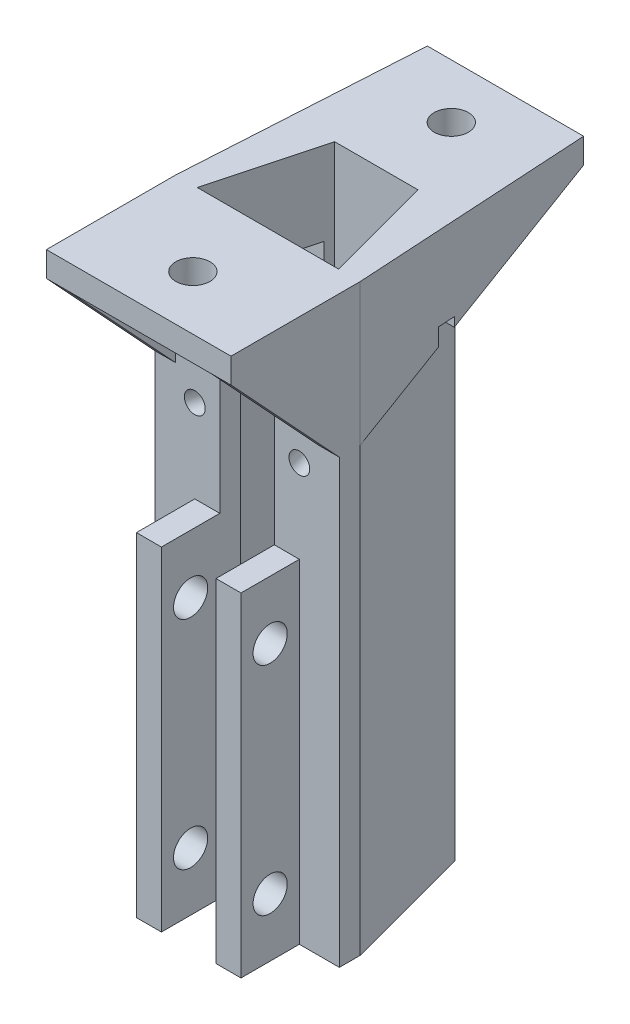
SolidWorks part; units mm, degrees
ref_plane "Front Plane" through (0, 0, 0) normal (0, 0, 1) x (1, 0, 0)
ref_plane "Top Plane" through (0, 0, 0) normal (0, 1, 0) x (1, 0, 0)
ref_plane "Right Plane" through (0, 0, 0) normal (1, 0, 0) x (0, 0, -1)
sketch "Sketch2" plane through (0, 0, 0) normal (0, 1, 0) x (1, 0, 0)
  line L0 (-8.0683, 3.8436) -> (5.7683, 3.8436)
  line L1 (-8.0683, 3.8436) -> (-8.0683, 1.3436)
  line L2 (5.7683, 3.8436) -> (5.7683, 1.3436)
  line L3 (-8.0683, 1.3436) -> (5.7683, 1.3436)
  line L4 (5.7683, 3.8436) -> (9.9215, -11.6564)
  line L5 (5.7683, 3.8436) -> (3.3535, 3.1965)
  line L6 (9.9215, -11.6564) -> (7.5067, -12.3035)
  line L7 (3.3535, 3.1965) -> (7.5067, -12.3035)
  line L8 (-8.0683, 3.8436) -> (-12.2215, -11.6564)
  line L9 (-8.0683, 3.8436) -> (-5.6535, 3.1965)
  line L10 (-12.2215, -11.6564) -> (-9.8067, -12.3035)
  line L11 (-5.6535, 3.1965) -> (-9.8067, -12.3035)
  line L12 (-12.2215, -11.6564) -> (-4.4215, -11.6564)
  line L13 (-12.2215, -11.6564) -> (-12.2215, -14.1564)
  line L14 (-4.4215, -11.6564) -> (-4.4215, -14.1564)
  line L15 (-12.2215, -14.1564) -> (-4.4215, -14.1564)
  line L16 (9.9215, -11.6564) -> (2.1215, -11.6564)
  line L17 (9.9215, -11.6564) -> (9.9215, -14.1564)
  line L18 (2.1215, -11.6564) -> (2.1215, -14.1564)
  line L19 (9.9215, -14.1564) -> (2.1215, -14.1564)
  line L20 (-4.4215, -14.1564) -> (-7.4215, -14.1564)
  line L21 (-4.4215, -14.1564) -> (-4.4215, -21.1564)
  line L22 (-7.4215, -14.1564) -> (-7.4215, -21.1564)
  line L23 (-4.4215, -21.1564) -> (-7.4215, -21.1564)
  line L24 (2.1215, -14.1564) -> (5.1215, -14.1564)
  line L25 (2.1215, -14.1564) -> (2.1215, -21.1564)
  line L26 (5.1215, -14.1564) -> (5.1215, -21.1564)
  line L27 (2.1215, -21.1564) -> (5.1215, -21.1564)
  point P0 (-6.15, 1.3436)
  point P21 (3.85, 1.3436)
  point P24 (7.3334, -11.6564)
  point P25 (-9.6333, -11.6564)
  dimension "D1" = 0
  dimension "D2" = 2.5
  dimension "D3" = 2.5
  dimension "D4" = 2.5
  dimension "D5" = 10
  dimension "D6" = 360
  dimension "D7" = 13
  dimension "D8" = 2.5
  dimension "D9" = 2.5
  dimension "D10" = 13
  dimension "D11" = 3
  dimension "D12" = 3
  dimension "D13" = 105
  dimension "D14" = 7.8
  dimension "D15" = 7.8
  dimension "D16" = 105
  dimension "D17" = 16.9667
  dimension "D18" = 6.5431
  dimension "D19" = 7
  dimension "D20" = 7
extrude "Boss-Extrude1" add sketch "Sketch2" along normal blind 40 contours L16 L4 L2 L3 L7 | L9 L11 L3 L7 L5 L0 | L8 L12 L11 L3 L1 | L5 L7 L3 L2 | L11 L9 L1 L3 | L13 L15 L14 L12 L11 L10 | L12 L10 L11 | L6 L16 L7 | L19 L17 L6 L7 L16 L18 | L25 L27 L26 L19 | L23 L21 L15 L22 region at (-7.0264, 0, -2.4857) region at (-9.164, 0, 4.9784) region at (-1.15, 0, -2.635) region at (6.8641, 0, 4.9784) region at (4.7264, 0, -2.4857) region at (-10.5538, 0, 11.8721) region at (-8.2214, 0, 12.9528) region at (5.9214, 0, 12.9528) region at (8.2539, 0, 11.8721) region at (-5.9215, 0, 17.6564) region at (3.6215, 0, 17.6564)
sketch "Sketch3" plane through (-7.4215, 0, 0) normal (-1, 0, 0) x (0, 0, 1)
  line L0 (21.1564, 40) -> (21.1564, 0) construction
  line L1 (14.1564, 40) -> (14.1564, 0) construction
  line L2 (14.1564, 40) -> (21.1564, 40) construction
  line L3 (14.1564, 0) -> (21.1564, 0) construction
  circle A0 centre (17.6564, 33) radius 2.05
  circle A1 centre (17.6564, 7) radius 2.05
  dimension "D5" = 4.1
  dimension "D6" = 4.1
  dimension "D1" = 3.5
  dimension "D2" = 3.5
  dimension "D3" = 3.5
  dimension "D4" = 3.5
  dimension "D7" = 7
  dimension "D8" = 7
extrude "Cut-Extrude2" cut sketch "Sketch3" against normal blind 40
sketch "Sketch4" plane through (0, 40, 0) normal (0, 1, 0) x (1, 0, 0)
  line L0 (-9.6333, -11.6564) -> (-6.15, 1.3436)
  line L1 (-6.15, 1.3436) -> (3.85, 1.3436)
  line L2 (3.85, 1.3436) -> (7.3334, -11.6564)
  line L3 (7.3334, -11.6564) -> (2.1215, -11.6564)
  line L4 (2.1215, -11.6564) -> (2.1215, -14.1564)
  line L5 (2.1215, -11.6564) -> (2.1215, -21.1564) construction
  line L6 (2.1215, -14.1564) -> (9.9215, -14.1564)
  line L7 (9.9215, -14.1564) -> (9.9215, -11.6564)
  line L8 (9.9215, -11.6564) -> (5.7683, 3.8436)
  line L9 (5.7683, 3.8436) -> (-8.0683, 3.8436)
  line L10 (-8.0683, 3.8436) -> (-12.2215, -11.6564)
  line L11 (-12.2215, -11.6564) -> (-12.2215, -14.1564)
  line L12 (-12.2215, -14.1564) -> (-4.4215, -14.1564)
  line L13 (-4.4215, -11.6564) -> (-4.4215, -21.1564) construction
  line L14 (-4.4215, -14.1564) -> (-4.4215, -11.6564)
  line L33 (-6.15, 1.3436) -> (3.85, 1.3436)
  line L34 (3.85, 1.3436) -> (7.3334, -11.6564)
  line L35 (7.3334, -11.6564) -> (2.1215, -11.6564)
  line L36 (2.1215, -11.6564) -> (2.1215, -21.1564)
  line L37 (2.1215, -21.1564) -> (5.1215, -21.1564)
  line L38 (5.1215, -21.1564) -> (5.1215, -14.1564)
  line L39 (5.1215, -14.1564) -> (9.9215, -14.1564)
  line L40 (9.9215, -14.1564) -> (9.9215, -11.6564)
  line L41 (9.9215, -11.6564) -> (5.7683, 3.8436)
  line L42 (5.7683, 3.8436) -> (-8.0683, 3.8436)
  line L43 (-8.0683, 3.8436) -> (-12.2215, -11.6564)
  line L44 (-12.2215, -11.6564) -> (-12.2215, -14.1564)
  line L45 (-12.2215, -14.1564) -> (-7.4215, -14.1564)
  line L46 (-7.4215, -14.1564) -> (-7.4215, -21.1564)
  line L47 (-7.4215, -21.1564) -> (-4.4215, -21.1564)
  line L48 (-4.4215, -21.1564) -> (-4.4215, -11.6564)
  line L49 (-4.4215, -11.6564) -> (-9.6333, -11.6564)
  line L50 (-9.6333, -11.6564) -> (-6.15, 1.3436)
  line L51 (-6.15, 1.3436) -> (3.85, 1.3436)
  line L52 (3.85, 1.3436) -> (7.3334, -11.6564)
  line L53 (7.3334, -11.6564) -> (2.1215, -11.6564)
  line L54 (2.1215, -11.6564) -> (2.1215, -21.1564)
  line L55 (2.1215, -21.1564) -> (5.1215, -21.1564)
  line L56 (5.1215, -21.1564) -> (5.1215, -14.1564)
  line L57 (5.1215, -14.1564) -> (9.9215, -14.1564)
  line L58 (9.9215, -14.1564) -> (9.9215, -11.6564)
  line L59 (9.9215, -11.6564) -> (5.7683, 3.8436)
  line L60 (5.7683, 3.8436) -> (-8.0683, 3.8436)
  line L61 (-8.0683, 3.8436) -> (-12.2215, -11.6564)
  line L62 (-12.2215, -11.6564) -> (-12.2215, -14.1564)
  line L63 (-12.2215, -14.1564) -> (-7.4215, -14.1564)
  line L64 (-7.4215, -14.1564) -> (-7.4215, -21.1564)
  line L65 (-7.4215, -21.1564) -> (-4.4215, -21.1564)
  line L66 (-4.4215, -21.1564) -> (-4.4215, -11.6564)
  line L68 (-9.6333, -11.6564) -> (-6.15, 1.3436)
  line M19 (-6.15, 1.3436) -> (3.85, 1.3436)
  line M20 (3.85, 1.3436) -> (7.3334, -11.6564)
  line M21 (7.3334, -11.6564) -> (2.1215, -11.6564)
  line M22 (2.1215, -11.6564) -> (2.1215, -21.1564)
  line M25 (5.1215, -14.1564) -> (9.9215, -14.1564)
  line M26 (9.9215, -14.1564) -> (9.9215, -11.6564)
  line M27 (9.9215, -11.6564) -> (5.7683, 3.8436)
  line M28 (5.7683, 3.8436) -> (-8.0683, 3.8436)
  line M29 (-8.0683, 3.8436) -> (-12.2215, -11.6564)
  line M30 (-12.2215, -11.6564) -> (-12.2215, -14.1564)
  line M31 (-12.2215, -14.1564) -> (-7.4215, -14.1564)
  line M34 (-4.4215, -21.1564) -> (-4.4215, -11.6564)
  line M35 (-4.4215, -11.6564) -> (-9.6333, -11.6564)
  line M36 (-9.6333, -11.6564) -> (-6.15, 1.3436)
  dimension "D1" = 0
extrude "Boss-Extrude2" add sketch "Sketch4" along normal blind 30 contours L12 L6 M31 M34 M35 M36 M19 M20 M21 M22 M25 M26 M27 M28 M29 M30 region at (-7.0274, 40, 11.9418)
sketch "Sketch16" plane through (0, 0, 14.1564) normal (0, 0, 1) x (1, 0, 0)
  line L0 (-4.4215, 70) -> (-4.4215, 40) construction
  line L1 (-12.2215, 70) -> (-4.4215, 70) construction
  circle A0 centre (-7.4215, 50) radius 1.25
  dimension "D1" = 20
  dimension "D2" = 2.5
  dimension "D4" = 3
extrude "Cut-Extrude9" cut sketch "Sketch16" along direction (-0.2588, 0, 0.9659) on the side against the normal blind 3.5
sketch "Sketch17" plane through (0, 0, 14.1564) normal (0, 0, 1) x (1, 0, 0)
  line L0 (2.1215, 70) -> (2.1215, 40) construction
  line L1 (2.1215, 70) -> (9.9215, 70) construction
  circle A0 centre (5.1215, 50) radius 1.25
  dimension "D1" = 2.5
  dimension "D2" = 3
  dimension "D3" = 20
extrude "Cut-Extrude10" cut sketch "Sketch17" along direction (0.2588, 0, 0.9659) on the side against the normal blind 3.5
sketch "Sketch18" plane through (0, 0, 11.6564) normal (0, 0, -1) x (-1, 0, 0)
  line L0 (-9.9215, 70) -> (-9.9215, 0) construction
  line L1 (-9.9215, 70) -> (12.2215, 70)
  line L2 (-9.9215, 70) -> (-9.9215, 67)
  line L3 (-9.9215, 67) -> (12.2215, 67)
  line L4 (12.2215, 70) -> (12.2215, 67)
  line L5 (12.2215, 70) -> (12.2215, 0) construction
  dimension "D1" = 3
  dimension "D2" = 0
extrude "Boss-Extrude4" add sketch "Sketch18" against normal blind 15.5
sketch "Sketch19" plane through (0, 0, -3.8436) normal (0, 0, -1) x (-1, 0, 0)
  line L0 (-5.7683, 70) -> (-5.7683, 0) construction
  line L1 (8.0683, 70) -> (-5.7683, 70)
  line L2 (8.0683, 70) -> (8.0683, 67)
  line L3 (8.0683, 67) -> (-5.7683, 67)
  line L4 (-5.7683, 70) -> (-5.7683, 67)
  dimension "D1" = 3
extrude "Boss-Extrude5" add sketch "Sketch19" along normal blind 13 and the other way blind 2 contours L1 L4 L3 L2
sketch "Sketch21" plane through (-12.2215, 0, 0) normal (-1, 0, 0) x (0, 0, 1)
  line L0 (27.1564, 67) -> (14.1564, 53)
  line L1 (14.1564, 67) -> (14.1564, 0) construction
  line L2 (14.1564, 53) -> (14.1564, 67)
  line L3 (14.1564, 67) -> (27.1564, 67)
  dimension "D1" = 14
extrude "Boss-Extrude6" add sketch "Sketch21" against normal blind 2.5
sketch "Sketch22" plane through (9.9215, 0, 0) normal (1, 0, 0) x (0, 0, -1)
  line L0 (-27.1564, 67) -> (-14.1564, 67)
  line L1 (-14.1564, 67) -> (-14.1564, 53)
  line L2 (-14.1564, 67) -> (-14.1564, 0) construction
  line L3 (-14.1564, 53) -> (-27.1564, 67)
  dimension "D1" = 14
extrude "Boss-Extrude8" add sketch "Sketch22" against normal blind 2.5
sketch "Sketch23" plane through (9.9215, 0, 0) normal (1, 0, 0) x (0, 0, -1)
  line L0 (-11.6564, 70) -> (-11.6564, 53)
  line L1 (-11.6564, 70) -> (-11.6564, 0) construction
  line L2 (16.8436, 70) -> (16.8436, 67)
  line L3 (16.8436, 70) -> (-11.6564, 70)
  line L4 (16.8436, 67) -> (-11.6564, 53)
  dimension "D1" = 28.5
  dimension "D2" = 28.5
  dimension "D3" = 17
  dimension "D4" = 3
extrude "Boss-Extrude9" add sketch "Sketch23" against normal blind 4.2
sketch "Sketch24" plane through (-12.2215, 0, 0) normal (-1, 0, 0) x (0, 0, 1)
  line L0 (11.6564, 70) -> (-16.8436, 70)
  line L1 (-16.8436, 70) -> (-16.8436, 67)
  line L2 (-16.8436, 67) -> (11.6564, 53)
  line L3 (11.6564, 70) -> (11.6564, 0) construction
  line L4 (11.6564, 53) -> (11.6564, 70)
  dimension "D1" = 17
  dimension "D2" = 28.5
  dimension "D3" = 3
extrude "Boss-Extrude10" add sketch "Sketch24" against normal blind 4.2
sketch "Sketch25" plane through (0, 70, 0) normal (0, 1, 0) x (1, 0, 0)
  line L2 (-6.15, 1.3436) -> (3.85, 1.3436) construction
  line L3 (5.7215, -11.6564) -> (-8.0215, -11.6564) construction
  circle A0 centre (-1.15, 10.3436) radius 2.05
  circle A1 centre (-1.15, -20.6564) radius 2.05
  dimension "D1" = 4.1
  dimension "D2" = 4.1
  dimension "D3" = 9
  dimension "D4" = 9
  dimension "D5" = 6.8715
  dimension "D6" = 6.8715
  dimension "D7" = 5
  dimension "D8" = 5
extrude "Cut-Extrude12" cut sketch "Sketch25" against normal blind 3.5
sketch "Sketch26" plane through (0, 47.3099, 23.2399) normal (0, -0.8976, -0.4409) x (-1, 0, 0)
  line L0 (-5.7215, 12.9056) -> (-7.3334, 12.9056)
  line L1 (-7.3334, 12.9056) -> (-5.7215, 19.6076)
  line L2 (-5.7215, 19.6076) -> (-5.7215, 12.9056)
  line L3 (8.0215, 12.9056) -> (8.0215, 19.6076)
  line L4 (8.0215, 19.6076) -> (9.6333, 12.9056)
  line L5 (9.6333, 12.9056) -> (8.0215, 12.9056)
extrude "Cut-Extrude13" cut sketch "Sketch26" along direction (0, -1, 0) on the side against the normal through all
sketch "Sketch27" plane through (0, 47.3099, 23.2399) normal (0, -0.8976, -0.4409) x (-1, 0, 0)
  line L0 (12.2215, 12.9056) -> (10.5215, 44.6586)
  line L1 (12.2215, 44.6586) -> (8.0215, 44.6586) construction
  line L2 (10.5215, 44.6586) -> (12.2215, 44.6586)
  line L3 (12.2215, 44.6586) -> (12.2215, 12.9056)
  line L4 (-9.9215, 12.9056) -> (-9.9215, 44.6586)
  line L5 (-9.9215, 44.6586) -> (-8.2215, 44.6586)
  line L6 (-5.7215, 44.6586) -> (-9.9215, 44.6586) construction
  line L7 (-8.2215, 44.6586) -> (-9.9215, 12.9056)
  dimension "D1" = 2.5
  dimension "D2" = 2.5
extrude "Cut-Extrude14" cut sketch "Sketch27" along direction (0, -1, 0) on the side against the normal through all
sketch "Sketch28" plane through (-12.2215, 0, 0) normal (-1, 0, 0) x (0, 0, 1)
  line L0 (-0.3436, 60) -> (-0.3436, 55.5)
  line L1 (-0.3436, 60) -> (1.6564, 60)
  line L2 (-0.3436, 55.5) -> (1.6564, 55.5)
  line L3 (1.6564, 60) -> (1.6564, 55.5)
  line L4 (11.6564, 70) -> (-16.8436, 70) construction
  line L5 (-1.3436, 70) -> (-1.3436, 0) construction
  dimension "D1" = 2
  dimension "D2" = 4.5
  dimension "D3" = 10
  dimension "D4" = 1
extrude "Cut-Extrude15" cut sketch "Sketch28" against normal through all
